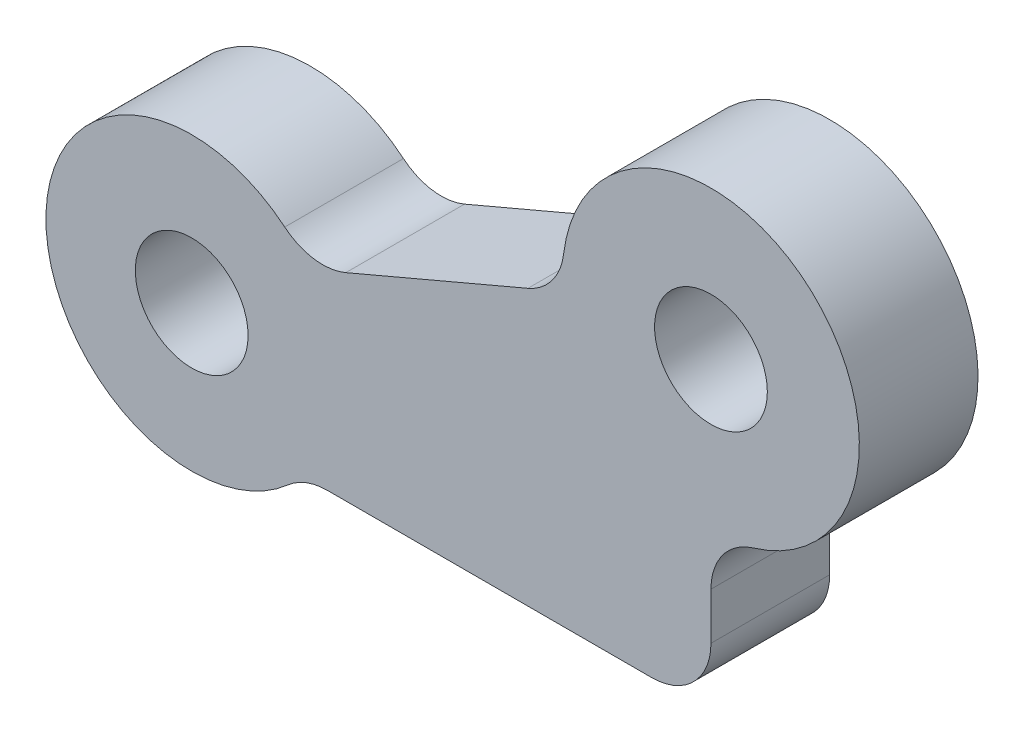
SolidWorks part; units mm, degrees
ref_plane "Front Plane" through (0, 0, 0) normal (0, 0, 1) x (1, 0, 0)
ref_plane "Top Plane" through (0, 0, 0) normal (0, 1, 0) x (1, 0, 0)
ref_plane "Right Plane" through (0, 0, 0) normal (1, 0, 0) x (0, 0, -1)
sketch "Sketch1" plane through (0, 0, 0) normal (0, 0, 1) x (1, 0, 0)
  line L0 (143.3333, 493) -> (716.6667, 493) construction
  line L1 (56.8391, 28.5799) -> (56.8391, 23.2923)
  line L2 (56.8391, 23.2923) -> (43.0826, 23.2923)
  line L3 (51.8645, 33.076) -> (43.2731, 29.4209)
  circle A2 centre (39.3406, 26.4759) radius 1.9
  circle A3 centre (56.8391, 33.5799) radius 1.9
  arc A4 (56.8391, 28.5799) -> (51.8645, 33.076) centre (56.8391, 33.5799) ccw
  arc A5 (43.2731, 29.4209) -> (43.0826, 23.2923) centre (39.3406, 26.4759) ccw
extrude "Boss-Extrude1" add sketch "Sketch1" along normal blind 4
fillet "Fillet1" radius 2 5 edges at (43.0826, 23.2923, 2) (56.8391, 23.2923, 2) (56.8391, 28.5799, 2) (43.2731, 29.4209, 2) (51.8645, 33.076, 2)
equation "\"D1@Fillet1\"=2"
